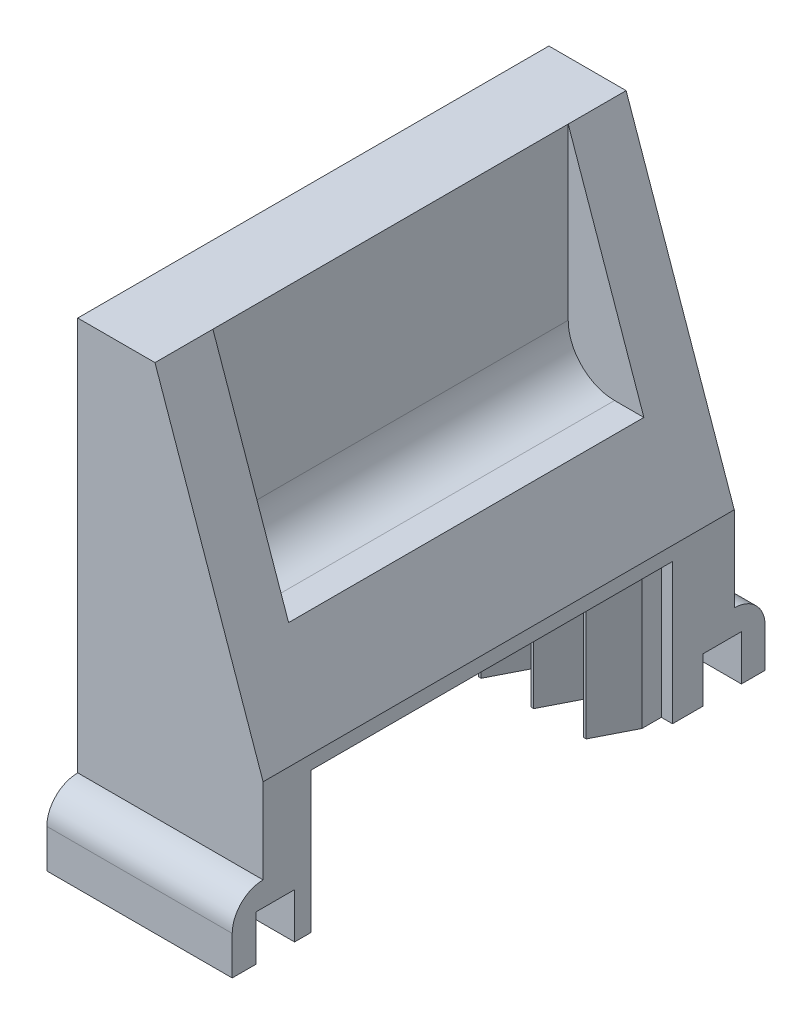
SolidWorks part; units mm, degrees
ref_plane "Front Plane" through (0, 0, 0) normal (0, 0, 1) x (1, 0, 0)
ref_plane "Top Plane" through (0, 0, 0) normal (0, 1, 0) x (1, 0, 0)
ref_plane "Right Plane" through (0, 0, 0) normal (1, 0, 0) x (0, 0, -1)
sketch "Sketch1" plane through (0, 0, 0) normal (0, 0, 1) x (1, 0, 0)
  line L0 (0, 0) -> (0, -30)
  line L1 (0, -30) -> (12, -30)
  line L2 (12, -30) -> (12, -20)
  line L3 (12, -20) -> (5, 0)
  line L4 (5, 0) -> (0, 0)
  dimension "D1" = 30
  dimension "D2" = 12
  dimension "D3" = 10
  dimension "D4" = 5
extrude "Boss-Extrude1" add sketch "Sketch1" against normal blind 30.5
sketch "Sketch4" plane through (0, 0, 0) normal (-1, 0, 0) x (0, 0, 1)
  line L0 (-30.5, 0) -> (-30.5, -30) construction
  line L1 (-26.5, -20.8999) -> (-3.1, -20.8999)
  line L2 (-26.5, -20.8999) -> (-26.5, -30.8999)
  line L3 (-26.5, -30.8999) -> (-3.1, -30.8999)
  line L4 (-3.1, -20.8999) -> (-3.1, -30.8999)
  point P4 (-26.5, -25.8999)
  dimension "D1" = 23.4
  dimension "D2" = 10
  dimension "D3" = 4
extrude "Cut-Extrude2" cut sketch "Sketch4" against normal blind 25 contours L2 L1 L4 L3
ref_plane "Plane1" through (0, 0, -15.25) normal (0, 0, 1) x (1, 0, 0)
sketch "Sketch6" plane through (0, 0, -15.25) normal (0, 0, 1) x (1, 0, 0)
  line L0 (5, 0) -> (5, -14)
  line L1 (5, -14) -> (9.9, -14)
  line L2 (12, -20) -> (5, 0) construction
  line L3 (9.9, -14) -> (5, 0)
  dimension "D1" = 14
extrude "Cut-Extrude4" cut sketch "Sketch6" against normal mid plane 23
ref_plane "Plane2" through (0, -26.4, 0) normal (0, 1, 0) x (1, 0, 0)
ref_plane "Plane3" through (0, -30, 0) normal (0, 1, 0) x (1, 0, 0)
sketch "Sketch7" plane through (0, -30, 0) normal (0, 1, 0) x (1, 0, 0)
  line L0 (11.2768, 26.95) -> (-19.7232, 26.95)
  line L62 (-6.6, 15.25) -> (6.6, 15.25) construction
  line L162 (11.2768, 26.95) -> (11.2768, 25.25)
  line L172 (-19.7232, 25.25) -> (-19.7232, 26.95)
  line L243 (11.2768, 25.25) -> (-19.7232, 25.25)
  dimension "D2" = 31
  dimension "D3" = 1.7
  dimension "D7" = 11.7
extrude "Boss-Extrude3" add sketch "Sketch7" along normal up to surface (9.1001 mm away) up to face at (6, -20.8999, -14.8)
sketch "Sketch10" plane through (0, -20.8999, 0) normal (0, 1, 0) x (1, 0, 0)
  line L0 (11.2768, 25.25) -> (10.058, 22.86)
  line L2 (10.058, 22.86) -> (9.8692, 22.86)
  line L3 (9.8692, 22.86) -> (8.6309, 25.25)
  line L4 (-19.7232, 25.25) -> (0, 25.25) construction
  line L5 (8.6309, 25.25) -> (11.2768, 25.25)
  point P3 (0, 0)
extrude "Boss-Extrude4" add sketch "Sketch10" against normal up to surface (9.1001 mm away) up to face at (0.8884, -30, -27.3)
pattern_linear "LPattern1" count 9 spacing 3.4 along (-1, 0, 0) of "Boss-Extrude4"
sketch "Sketch11" plane through (0, 0, -30.5) normal (0, 0, -1) x (-1, 0, 0)
  line L0 (-12, -30) -> (-12, -20) construction
  line L1 (-12, -25.5) -> (0, -25.5)
  line L2 (-12, -25.5) -> (-12, -30)
  line L3 (-12, -30) -> (0, -30)
  line L4 (0, -25.5) -> (0, -30)
  dimension "D1" = 4.5
extrude "Boss-Extrude5" add sketch "Sketch11" along normal blind 2
fillet "Fillet1" radius 2 1 edges at (6, -25.5, -32.5)
mirror "Mirror1" about plane through (0, 0, -15.25) normal (0, 0, 1) of "Boss-Extrude5"
fillet "Fillet2" radius 2 1 edges at (6, -25.5, 2)
fillet "Fillet5" radius 3 1 edges at (5, -14, -15.25)
sketch "Sketch12" plane through (0, 0, 0) normal (-1, 0, 0) x (0, 0, 1)
  line L0 (-15.25, -20.6354) -> (-15.25, -36.9741) construction
  line L1 (-30.9639, -27.0644) -> (-28.4639, -27.0644)
  line L2 (-30.9639, -27.0644) -> (-30.9639, -30.5644)
  line L3 (-30.9639, -30.5644) -> (-28.4639, -30.5644)
  line L4 (-28.4639, -27.0644) -> (-28.4639, -30.5644)
  line L11 (-15.25, -16.5) -> (-15.25, 16.5) construction
  line L12 (0.4639, -30.5644) -> (-2.0361, -30.5644)
  line L13 (-2.0361, -27.0644) -> (-2.0361, -30.5644)
  line L14 (0.4639, -27.0644) -> (-2.0361, -27.0644)
  line L15 (0.4639, -27.0644) -> (0.4639, -30.5644)
  point P6 (-15.25, -20.6354)
  point P8 (-13.1192, -20.8999)
  dimension "D1" = 2.5
  dimension "D2" = 3.5
extrude "Cut-Extrude5" cut sketch "Sketch12" against normal up to surface (12 mm away) up to face at (12, -25.581, -15.1)
